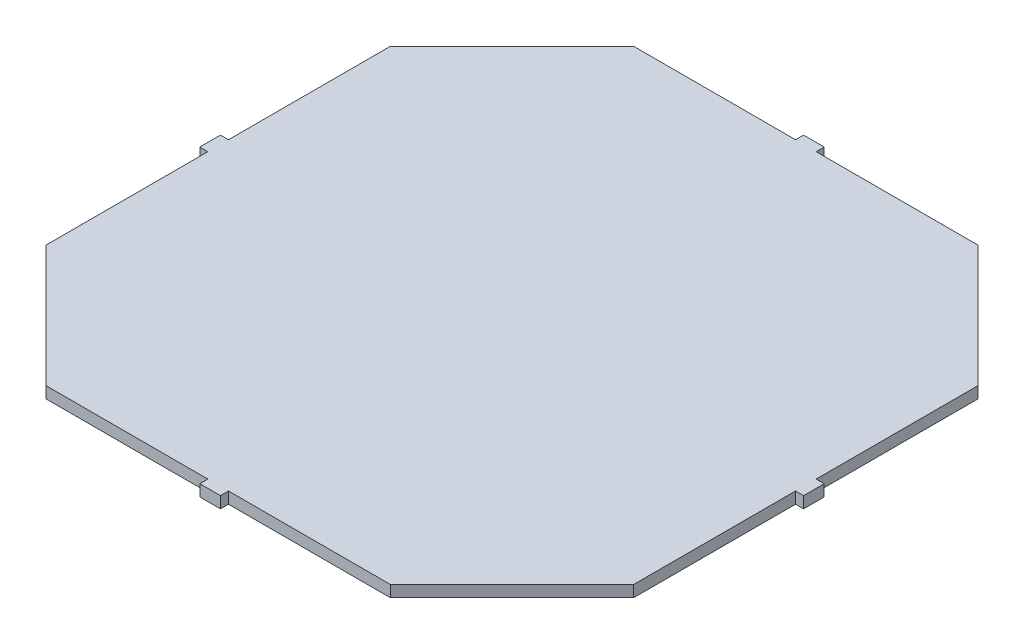
SolidWorks part; units mm, degrees
material "Acrylic (Medium-high impact)"
ref_plane "Front Plane" through (0, 0, 0) normal (0, 0, 1) x (1, 0, 0)
ref_plane "Top Plane" through (0, 0, 0) normal (0, 1, 0) x (1, 0, 0)
ref_plane "Right Plane" through (0, 0, 0) normal (1, 0, 0) x (0, 0, -1)
sketch "Sketch1" plane through (0, 0, 0) normal (0, 1, 0) x (1, 0, 0)
  line L0 (-25.6066, 15) -> (-15, 25.6066)
  line L1 (-15, -25.6066) -> (15, -25.6066)
  line L2 (-25.6066, -15) -> (-25.6066, 15)
  line L3 (-15, 25.6066) -> (15, 25.6066)
  line L4 (25.6066, -15) -> (25.6066, 15)
  line L5 (-20.3033, -20.3033) -> (20.3033, 20.3033) construction
  line L6 (-20.3033, 20.3033) -> (20.3033, -20.3033) construction
  line L7 (-25.6066, -15) -> (-15, -25.6066)
  line L8 (15, -25.6066) -> (25.6066, -15)
  line L9 (15, 25.6066) -> (25.6066, 15)
  point P0 (0, 0)
  dimension "D1" = 30
  dimension "D2" = 30
  dimension "D3" = 135
  dimension "D4" = 135
  dimension "D5" = 15
  dimension "D6" = 135
extrude "Boss-Extrude1" add sketch "Sketch1" along normal blind 1
sketch "Sketch2" plane through (0, 1, 0) normal (0, 1, 0) x (1, 0, 0)
  line L0 (0, 25.6066) -> (0, -25.6066) construction
  line L1 (15, 25.6066) -> (-15, 25.6066) construction
  line L2 (-15, -25.6066) -> (15, -25.6066) construction
  line L3 (-25.6066, 0) -> (25.6066, 0) construction
  line L4 (-25.6066, 15) -> (-25.6066, -15) construction
  line L5 (25.6066, -15) -> (25.6066, 15) construction
  line L6 (-25.6066, 0.9) -> (-26.3066, 0.9)
  line L7 (-26.3066, 0.9) -> (-26.3066, -0.9)
  line L8 (-26.3066, -0.9) -> (-25.6066, -0.9)
  line L9 (-0.9, 25.6066) -> (-0.9, 26.3066)
  line L10 (-0.9, 26.3066) -> (0.9, 26.3066)
  line L11 (0.9, 26.3066) -> (0.9, 25.6066)
  line L12 (0.9, -26.3066) -> (0.9, -25.6066)
  line L13 (-0.9, -26.3066) -> (0.9, -26.3066)
  line L14 (-0.9, -25.6066) -> (-0.9, -26.3066)
  line L15 (26.3066, -0.9) -> (25.6066, -0.9)
  line L16 (26.3066, 0.9) -> (26.3066, -0.9)
  line L17 (25.6066, 0.9) -> (26.3066, 0.9)
  line L18 (-0.9, 25.6066) -> (0.9, 25.6066)
  line L19 (25.6066, 0.9) -> (25.6066, -0.9)
  line L20 (-0.9, -25.6066) -> (0.9, -25.6066)
  line L21 (-25.6066, -0.9) -> (-25.6066, 0.9)
  dimension "D1" = 1.8
  dimension "D2" = 0.7
  dimension "D3" = 1.8
  dimension "D4" = 0.7
extrude "Boss-Extrude2" add sketch "Sketch2" against normal blind 1
